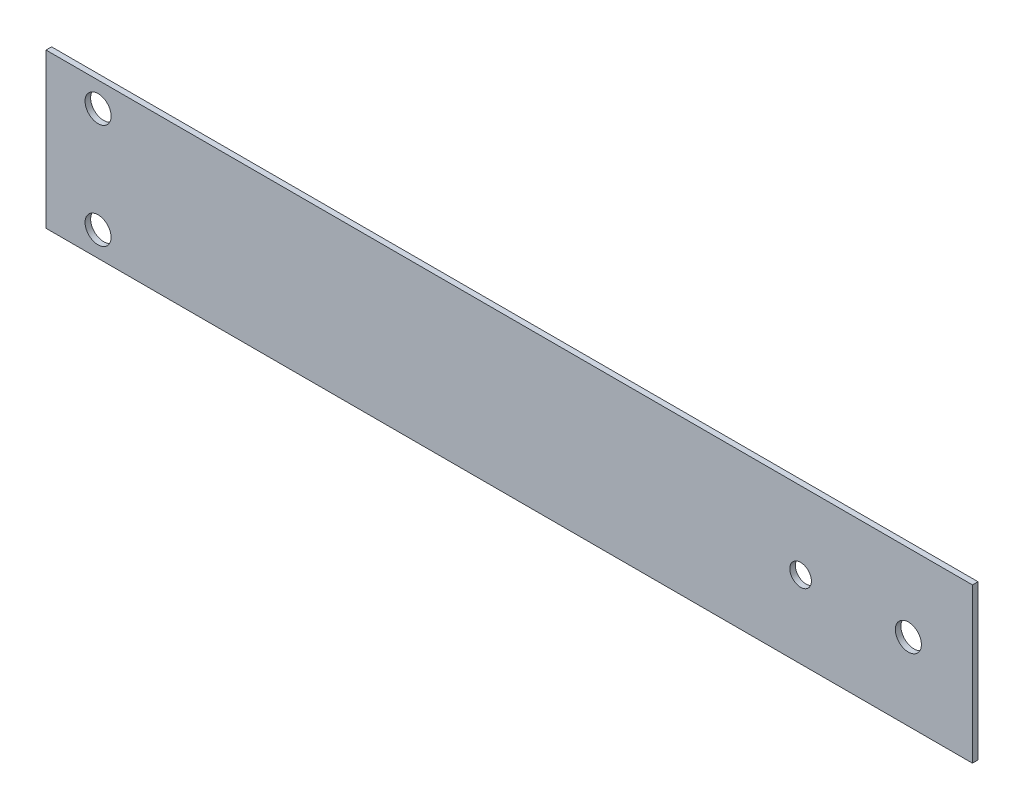
SolidWorks part; units mm, degrees
ref_plane "Front Plane" through (0, 0, 0) normal (0, 0, 1) x (1, 0, 0)
ref_plane "Top Plane" through (0, 0, 0) normal (0, 1, 0) x (1, 0, 0)
ref_plane "Right Plane" through (0, 0, 0) normal (1, 0, 0) x (0, 0, -1)
sketch "Sketch2" plane through (0, 0, 0) normal (0, 0, 1) x (1, 0, 0)
  line L0 (75, 12.5) -> (-75, -12.5) construction
  line L1 (-75, 12.5) -> (75, 12.5)
  line L2 (-75, 12.5) -> (-75, -12.5)
  line L3 (-75, -12.5) -> (75, -12.5)
  line L4 (75, 12.5) -> (75, -12.5)
  point P4 (0, 0)
  dimension "D1" = 150
  dimension "D2" = 25
base flange "Base-Flange1" sketch "Sketch2" thickness 0.9 reverse thickness direction no parameters "D1"=1
hole_wizard "#19 (0.166) Diameter Slot1" positions "Sketch8" profile "Sketch7" size "#19" standard "ANSI Inch" slot yes end condition through all
sketch "Sketch8" plane through (0, 0, -0.9) normal (0, 0, -1) x (-1, 0, 0)
  point P1 (-64.628, 0)
sketch "Sketch7" plane through (64.628, 0, -0.9) normal (1, 0, 0) x (0, 1, 0)
  line L0 (0, 0) -> (0, 0.9)
  line L1 (0, 0.9) -> (2.1082, 0.9)
  line L2 (2.1082, 0.9) -> (2.1082, 0)
  line L5 (2.1082, 0) -> (0, 0)
  line L11 (0, -6.35) -> (0, 107.95) construction
  dimension "Thru Hole Dia." = 4.2164
  dimension "Thru Hole Depth" = 0.9
hole_wizard "#19 (0.166) Diameter Slot2" positions "Sketch11" profile "Sketch9" size "#19" standard "ANSI Inch" slot yes end condition through all
sketch "Sketch11" plane through (0, 0, 0) normal (0, 0, 1) x (1, 0, 0)
  line L0 (-75, -12.5) -> (75, -12.5) construction
  line L1 (75, 12.5) -> (-75, 12.5) construction
  point P0 (-66.5679, 8.5)
  point P2 (-66.5679, -8.5)
  dimension "D1" = 4
  dimension "D2" = 4
sketch "Sketch9" plane through (-66.5679, 8.5, 0) normal (1, 0, 0) x (0, -1, 0)
  line L0 (0, 0) -> (0, 0.9)
  line L1 (0, 0.9) -> (2.1082, 0.9)
  line L2 (2.1082, 0.9) -> (2.1082, 0)
  line L5 (2.1082, 0) -> (0, 0)
  line L11 (0, -6.35) -> (0, 107.95) construction
  dimension "Thru Hole Dia." = 4.2164
  dimension "Thru Hole Depth" = 0.9
hole_wizard "Ø1.0mm Dowel Slot1" positions "Sketch13" profile "Sketch12" size "Ø1.0" standard "ANSI Metric" slot yes end condition through all
sketch "Sketch13" plane through (0, 0, 0) normal (0, 0, 1) x (1, 0, 0)
  circle A0 centre (64.628, 1.089) radius 2.1082 construction
  point P0 (47.178, 0)
  dimension "D1" = 17.45
sketch "Sketch12" plane through (47.178, 0, 0) normal (1, 0, 0) x (0, -1, 0)
  line L0 (0, 0) -> (0, 0.9)
  line L1 (0, 0.9) -> (1.75, 0.9)
  line L2 (1.75, 0.9) -> (1.75, 0)
  line L5 (1.75, 0) -> (0, 0)
  line L11 (0, -6.35) -> (0, 107.95) construction
  dimension "Thru Hole Dia." = 3.5
  dimension "Thru Hole Depth" = 0.9
sketch "Bend-Lines1" plane through (0, 0, 0) normal (0, 1, 0) x (1, 0, 0)
sketch "Bounding-Box1" plane through (0, 0, 0) normal (0, 1, 0) x (1, 0, 0)
sheet metal parameters "Sheet-Metal1" thickness 0.9 parameters "D1"=3
flat pattern "Flat-Pattern1" [suppressed]
sketch "Bend-Lines2" plane through (0, 0, 0) normal (0, 1, 0) x (1, 0, 0)
sketch "Bounding-Box2" [suppressed] plane through (0, 0, 0) normal (0, 1, 0) x (1, 0, 0)
sheet metal parameters "Sheet-Metal2" thickness 0.9 parameters "D1"=3
flat pattern "Flat-Pattern1"
sketch "Bend-Lines2" plane through (0, 0, 0) normal (0, 1, 0) x (1, 0, 0)
sketch "Bounding-Box2" [suppressed] plane through (0, 0, 0) normal (0, 1, 0) x (1, 0, 0)
sheet metal parameters "Sheet-Metal3" thickness 0.9 parameters "D1"=3
flat pattern "Flat-Pattern1"
sketch "Bend-Lines2" plane through (0, 0, 0) normal (0, 1, 0) x (1, 0, 0)
sketch "Bounding-Box2" [suppressed] plane through (0, 0, 0) normal (0, 1, 0) x (1, 0, 0)
sheet metal parameters "Sheet-Metal4" thickness 0.9 parameters "D1"=3
flat pattern "Flat-Pattern1"
sketch "Bend-Lines2" plane through (0, 0, 0) normal (0, 1, 0) x (1, 0, 0)
sketch "Bounding-Box2" [suppressed] plane through (0, 0, 0) normal (0, 1, 0) x (1, 0, 0)
